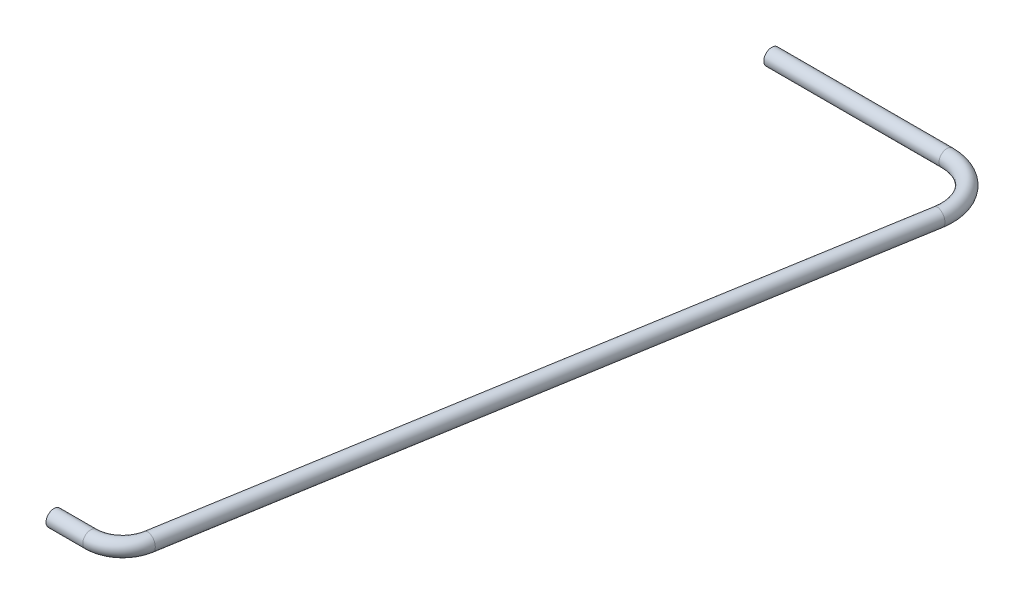
SolidWorks part; units mm, degrees
ref_plane "Front Plane" through (0, 0, 0) normal (0, 0, 1) x (1, 0, 0)
ref_plane "Top Plane" through (0, 0, 0) normal (0, 1, 0) x (1, 0, 0)
ref_plane "Right Plane" through (0, 0, 0) normal (1, 0, 0) x (0, 0, -1)
sketch "Sketch1" plane through (0, 0, 0) normal (0, 1, 0) x (1, 0, 0)
  line L1 (-5, 0) -> (6.5408, 0)
  line L2 (16.4024, 8.3421) -> (52.0602, 220.4467)
  line L3 (37.2678, 237.9335) -> (-17.7322, 237.9335)
  arc A0 (52.0602, 220.4467) -> (37.2678, 237.9335) centre (37.2678, 222.9335) ccw
  arc A1 (16.4024, 8.3421) -> (6.5408, 0) centre (6.5408, 10) cw
  point P11 (15, 0)
  dimension "D1" = 15
  dimension "D2" = 20
  dimension "D3" = 10
  dimension "D4" = 55
sweep "Sweep1" add path "Sketch1" circular profile diameter 5 parameters "D3"=5
